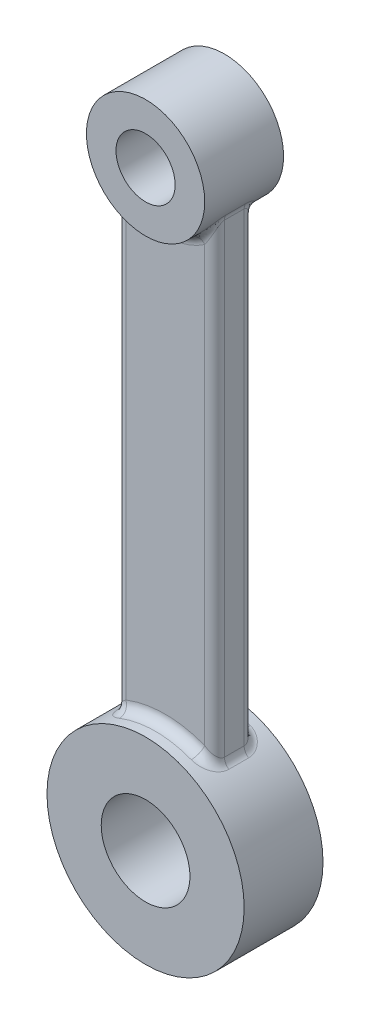
SolidWorks part; units mm, degrees
ref_plane "Front Plane" through (0, 0, 0) normal (0, 0, 1) x (1, 0, 0)
ref_plane "Top Plane" through (0, 0, 0) normal (0, 1, 0) x (1, 0, 0)
ref_plane "Right Plane" through (0, 0, 0) normal (1, 0, 0) x (0, 0, -1)
sketch "Sketch1" plane through (0, 0, 0) normal (0, 1, 0) x (1, 0, 0)
  line L1 (2.5, -1) -> (-2.5, -1)
  line L2 (2.5, -1) -> (2.5, 1)
  line L3 (2.5, 1) -> (-2.5, 1)
  line L4 (-2.5, -1) -> (-2.5, 1)
  line L5 (2.5, -1) -> (-2.5, 1) construction
  line L6 (2.5, 1) -> (-2.5, -1) construction
  point P0 (0, 0)
  dimension "D1" = 5
  dimension "D2" = 2
extrude "Boss-Extrude1" add sketch "Sketch1" along normal mid plane 30
sketch "Sketch4" plane through (0, 0, 0) normal (0, 0, 1) x (1, 0, 0)
  line L0 (2.5, 15) -> (-2.5, 15) construction
  line L1 (2.5, -15) -> (-2.5, -15) construction
  circle A0 centre (0, 15) radius 3
  circle A1 centre (0, -15) radius 5
  dimension "D1" = 10
  dimension "D2" = 6
extrude "Boss-Extrude3" add sketch "Sketch4" along normal mid plane 4
sketch "Sketch5" plane through (0, 0, -2) normal (0, 0, -1) x (-1, 0, 0)
  circle A0 centre (0, 15) radius 1.5
  circle A1 centre (0, -15) radius 2.25
  dimension "D1" = 3
  dimension "D2" = 4.5
extrude "Cut-Extrude2" cut sketch "Sketch5" against normal through all
fillet "Fillet1" radius 0.5 4 edges at (2.5, 1.3359, 1) (2.5, 1.3359, -1) (-2.5, 1.3359, 1) (-2.5, 1.3359, -1)
fillet "Fillet2" radius 0.5 8 edges at (-2.4553, 13.2762, 0.7066) (-2.5, 13.3417, 0) (-2.3986, 13.1981, -0.8019) (0, 12, -1) (2.4553, 13.2762, -0.7066) (2.5, 13.3417, 0) (0, 12, 1) (2.3986, 13.1981, 0.8019)
fillet "Fillet3" radius 0.5 8 edges at (0, -10, -1) (-2.4123, -10.6204, -0.7829) (-2.5, -10.6699, 0) (-2.3376, -10.5801, 0.8688) (2.3376, -10.5801, -0.8688) (0, -10, 1) (2.4123, -10.6204, 0.7829) (2.5, -10.6699, 0)
